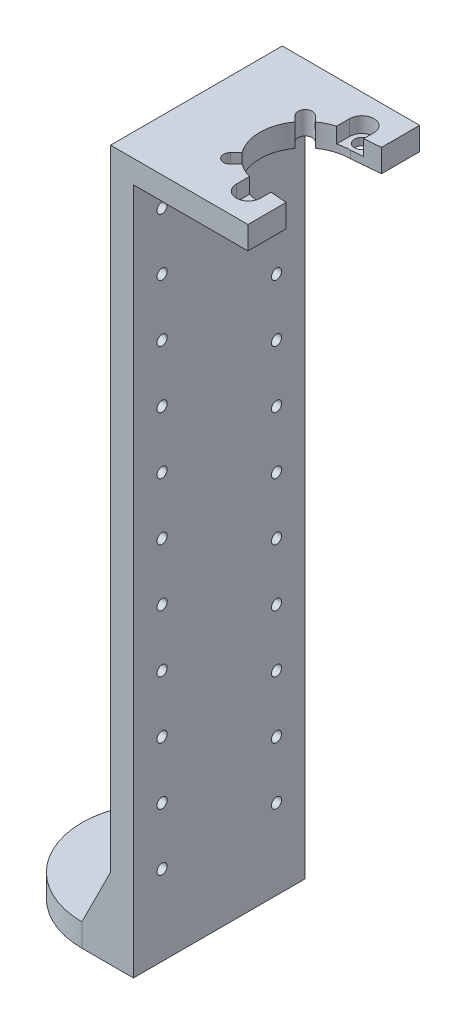
SolidWorks part; units mm, degrees
material "Copper"
ref_plane "Front Plane" through (0, 0, 0) normal (0, 0, 1) x (1, 0, 0)
ref_plane "Top Plane" through (0, 0, 0) normal (0, 1, 0) x (1, 0, 0)
ref_plane "Right Plane" through (0, 0, 0) normal (1, 0, 0) x (0, 0, -1)
sketch "Sketch1" plane through (0, 0, 0) normal (0, 0, 1) x (1, 0, 0)
  line L0 (0, 0) -> (0, 120)
  line L1 (0, 120) -> (24, 120)
  line L2 (24, 120) -> (24, 116)
  line L3 (24, 116) -> (4, 116)
  line L4 (4, 116) -> (4, -4)
  line L5 (4, -4) -> (-20, -4)
  line L6 (-20, -4) -> (-20, 0)
  line L7 (-20, 0) -> (0, 0)
  dimension "D1" = 24
  dimension "D2" = 24
  dimension "D3" = 20
  dimension "D4" = 4
  dimension "D5" = 4
  dimension "D6" = 120
  dimension "D7" = 120
extrude "BracketMainBody" add sketch "Sketch1" along normal mid plane 30
sketch "M4_thruHole" plane through (0, -4, 0) normal (0, -1, 0) x (1, 0, 0)
  line L0 (-20, 15) -> (-20, -15) construction
  circle A0 centre (-10, 0) radius 2.4
  dimension "D1" = 4.8
  dimension "D2" = 10
  dimension "D3" = 10
sketch "SQUIDcutouts" plane through (0, 0, 0) normal (0, 1, 0) x (1, 0, 0)
  line L0 (24, -15) -> (24, 15) construction
  line L3 (0, -15) -> (0, 15) construction
  line L4 (24, 0) -> (4, 0) construction
  line L5 (12.6003, 4.6319) -> (11.6161, 5.6161)
  line L6 (13.3839, 7.3839) -> (14.3681, 6.3997)
  line L7 (11.6161, -5.6161) -> (12.6003, -4.6319)
  line L9 (13.3839, -7.3839) -> (14.3681, -6.3997)
  circle A0 centre (19, -9.9) radius 1.3
  circle A1 centre (19, 9.9) radius 1.3
  arc A2 (12.6003, 4.6319) -> (12.6003, -4.6319) centre (19, 0) ccw
  arc A3 (13.3839, 7.3839) -> (11.6161, 5.6161) centre (12.5, 6.5) ccw
  arc A4 (11.6161, -5.6161) -> (13.3839, -7.3839) centre (12.5, -6.5) ccw
  arc A5 (14.3681, -6.3997) -> (14.3681, 6.3997) centre (19, 0) ccw
  dimension "D1" = 5
  dimension "D3" = 2.6
  dimension "D4" = 2.6
  dimension "D9" = 15.8
  dimension "D12" = 2.5
  dimension "D15" = 2.5
  dimension "D18" = 1.3919
  dimension "D2" = 9.9
  dimension "D5" = 5
  dimension "D6" = 9.9
  dimension "D7" = 5
  dimension "D10" = 6.5
  dimension "D11" = 12.5
  dimension "D13" = 6.5
  dimension "D14" = 12.5
  dimension "D16" = 1.3919
  dimension "D17" = 1.3919
  dimension "D19" = 7.9424
extrude "CutExtrude_SQUIDcutouts" cut sketch "SQUIDcutouts" against normal through all from surface contours A0 | A1 | A5 L6 A3 L5 A2 L7 A4 L9 starting at face at (12, 120, 0)
sketch "champhers" plane through (0, 120, 0) normal (0, 1, 0) x (1, 0, 0)
  line L0 (24, 8.3374) -> (24, 6.1164)
  line L1 (24, 6.1164) -> (24, 15) construction
  line L2 (24, 8.3374) -> (19, 7.9)
  line L4 (30.1328, 0) -> (13.0253, 0) construction
  line L5 (24, -6.1164) -> (19, -7.9)
  line L6 (24, -8.3374) -> (19, -7.9)
  line L7 (24, -8.3374) -> (24, -6.1164)
  line L9 (19, 7.9) -> (24, 6.1164)
  arc A0 (14.3681, -6.3997) -> (14.3681, 6.3997) centre (19, 0) ccw construction
  dimension "D2" = 85
extrude "Cut-Extrude7" [suppressed] cut sketch "champhers" against normal through all
sketch "Sketch13" plane through (0, 120, 0) normal (0, 1, 0) x (1, 0, 0)
  line L0 (19, 9.9) -> (19, -9.9) construction
  line L5 (21.1241, 9.9) -> (21.1241, -9.9)
  line L6 (16.8759, 9.9) -> (16.8759, -9.9)
  arc A3 (21.1241, 9.9) -> (16.8759, 9.9) centre (19, 9.9) ccw
  arc A4 (16.8759, -9.9) -> (21.1241, -9.9) centre (19, -9.9) ccw
  point P3 (19, 0)
  dimension "D1" = 19.8
  dimension "D2" = 2.1241
ref_plane "M2CounterBore_offsetTopPlane" through (0, 117.3, 0) normal (0, 1, 0) x (1, 0, 0)
hole_wizard "M4 Clearance Hole1" positions "3DSketch1" profile "Sketch18" hole size "M4" standard "ANSI Metric" end condition up to next
sketch3d "3DSketch1"
  point P0 (-10, -4, 0)
sketch "Sketch18" plane through (-10, -4, 0) normal (1, 0, 0) x (0, 0, -1)
  line L0 (0, 0) -> (0, 4)
  line L1 (0, 4) -> (2.25, 4)
  line L2 (2.25, 4) -> (2.25, 0)
  line L5 (2.25, 0) -> (0, 0)
  line L11 (0, -6.35) -> (0, 107.95) construction
  dimension "Thru Hole Dia." = 4.5
  dimension "Thru Hole Depth" = 4
extrude "Cut-Extrude12" cut sketch "champhers<2>" against normal up to next
sketch "champhers<2>" plane through (0, 120, 0) normal (0, 1, 0) x (1, 0, 0) same geometry as "champhers"
fillet "Fillet11" radius 15 1 edges at (-20, -2, -15)
fillet "Fillet12" radius 15 1 edges at (-20, -2, 15)
fillet "Fillet13" [suppressed] radius 7.54
sketch "Sketch24" plane through (0, 0, 0) normal (1, 0, 0) x (0, 0, -1)
  line L0 (0, 0) -> (0, 120) construction
  line L1 (-15, 120) -> (15, 120) construction
  point P0 (10, 110)
  dimension "D1" = 10
  dimension "D2" = 10
hole_wizard "#2-56 Tapped Hole1" positions "3DSketch5" profile "Sketch25" tap size "#2-56" standard "ANSI Inch" end condition up to next
sketch3d "3DSketch5"
  line L0 (0, 0, 0) -> (0, 120, 0) construction
  line L1 (0, 120, 15) -> (0, 120, -15) construction
  point P4 (0, 110, -10)
  dimension "D1" = 10
  dimension "D2" = 10
sketch "Sketch25" plane through (0, 110, -10) normal (0, 1, 0) x (0, 0, 1)
  line L0 (0, 0) -> (0, 4.001)
  line L1 (0, 4.001) -> (0.889, 4.001)
  line L2 (0.889, 4.001) -> (0.889, 0)
  line L5 (0.889, 0) -> (0, 0)
  line L11 (0, -6.35) -> (0, 107.95) construction
  dimension "Thru Tap Drill Dia." = 1.778
  dimension "Thru Tap Drill Depth" = 4.001
cosmetic thread "Hole Thread2" parameters "D2"=2.1844
pattern_linear "LPattern3" count 11 spacing 10 along (0, -1, 0) count 2 spacing 20 along (0, 0, 1) of "#2-56 Tapped Hole1"
cosmetic thread "Hole Thread3" parameters "D2"=2.1844
cosmetic thread "Hole Thread4" parameters "D2"=2.1844
cosmetic thread "Hole Thread5" parameters "D2"=2.1844
cosmetic thread "Hole Thread6" parameters "D2"=2.1844
cosmetic thread "Hole Thread7" parameters "D2"=2.1844
cosmetic thread "Hole Thread8" parameters "D2"=2.1844
cosmetic thread "Hole Thread9" parameters "D2"=2.1844
cosmetic thread "Hole Thread10" parameters "D2"=2.1844
cosmetic thread "Hole Thread11" parameters "D2"=2.1844
cosmetic thread "Hole Thread12" parameters "D2"=2.1844
cosmetic thread "Hole Thread13" parameters "D2"=2.1844
cosmetic thread "Hole Thread14" parameters "D2"=2.1844
cosmetic thread "Hole Thread15" parameters "D2"=2.1844
cosmetic thread "Hole Thread16" parameters "D2"=2.1844
cosmetic thread "Hole Thread17" parameters "D2"=2.1844
cosmetic thread "Hole Thread18" parameters "D2"=2.1844
cosmetic thread "Hole Thread19" parameters "D2"=2.1844
cosmetic thread "Hole Thread20" parameters "D2"=2.1844
cosmetic thread "Hole Thread21" parameters "D2"=2.1844
cosmetic thread "Hole Thread22" parameters "D2"=2.1844
cosmetic thread "Hole Thread23" parameters "D2"=2.1844
cosmetic thread "Hole Thread24" parameters "D2"=2.1844
cosmetic thread "Hole Thread25" parameters "D2"=2.1844
extrude "Cut-Extrude14" cut sketch "Sketch13" against normal up to surface (2.7 mm away) contours L5 A4 L6 A3 up to plane "M2CounterBore_offsetTopPlane"
sketch "Sketch28" plane through (0, 0, -15) normal (0, 0, -1) x (-1, 0, 0)
  line L0 (-24, 120) -> (-24, 116)
  line L1 (-24, 120) -> (0, 120)
  line L2 (0, 120) -> (0, 108)
  line L3 (0, 120) -> (0, 0) construction
  line L4 (0, 108) -> (-4, 108)
  line L5 (-4, -4) -> (-4, 116) construction
  line L7 (-4, 116) -> (-24, 116) construction
  line L8 (-12, 116) -> (-4, 108)
  line L9 (-24, 116) -> (-12, 116)
  dimension "D1" = 12
  dimension "D2" = 24
  dimension "D3" = 4
  dimension "D4" = 12
sketch "Sketch29" plane through (0, 0, 15) normal (0, 0, 1) x (1, 0, 0)
  line L0 (24, 120) -> (0, 120)
  line L1 (24, 120) -> (0, 120) construction
  line L2 (0, 120) -> (0, 108)
  line L3 (0, 120) -> (0, 0) construction
  line L4 (0, 108) -> (4, 108)
  line L5 (4, -4) -> (4, 116) construction
  line L7 (4, 116) -> (24, 116) construction
  line L8 (12, 116) -> (4, 108)
  line L9 (24, 120) -> (24, 116)
  line L10 (24, 116) -> (12, 116)
  dimension "D1" = 24
  dimension "D2" = 12
  dimension "D3" = 4
  dimension "D4" = 12
sketch "Sketch30" plane through (0, 0, 15) normal (0, 0, 1) x (1, 0, 0)
  line L0 (-5, 0) -> (0, 0)
  line L1 (-20, 0) -> (0, 0) construction
  line L2 (0, 0) -> (0, 10)
  line L3 (0, 0) -> (0, 120) construction
  line L4 (0, 10) -> (-5, 0)
  dimension "D1" = 10
  dimension "D2" = 5
extrude "Boss-Extrude3" add sketch "Sketch30" against normal blind 2
sketch "Sketch31" plane through (0, 0, -15) normal (0, 0, -1) x (-1, 0, 0)
  line L0 (0, 10) -> (0, 0)
  line L1 (0, 120) -> (0, 0) construction
  line L2 (0, 0) -> (5, 0)
  line L3 (0, 0) -> (5, 0) construction
  line L4 (5, 0) -> (0, 10)
  dimension "D1" = 10
  dimension "D2" = 5
extrude "Boss-Extrude4" add sketch "Sketch31" against normal blind 2
fillet "Fillet17" radius 3.5 1 edges at (-2.5, 0, -13)
fillet "Fillet18" radius 3.5 1 edges at (-2.5, 0, 13)
sketch "Sketch32" plane through (0, 116, 0) normal (0, -1, 0) x (1, 0, 0)
  circle A0 centre (19, 0) radius 13.5
  dimension "D1" = 27
